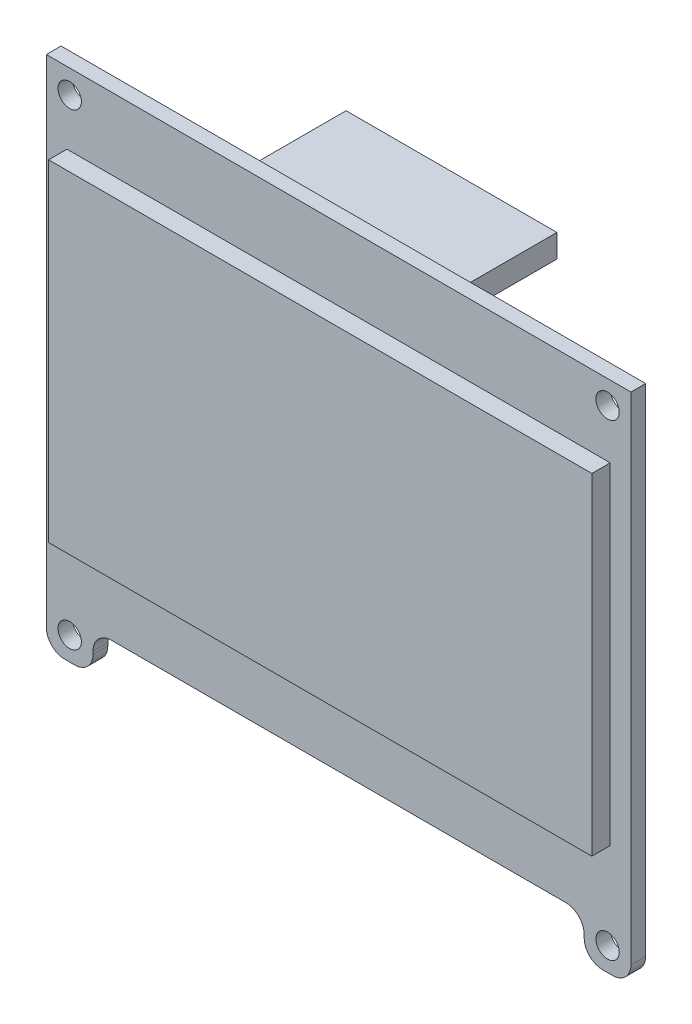
SolidWorks part; units mm, degrees
ref_plane "Front Plane" through (0, 0, 0) normal (0, 0, 1) x (1, 0, 0)
ref_plane "Top Plane" through (0, 0, 0) normal (0, 1, 0) x (1, 0, 0)
ref_plane "Right Plane" through (0, 0, 0) normal (1, 0, 0) x (0, 0, -1)
sketch "Sketch1" plane through (0, 0, 0) normal (0, 0, 1) x (1, 0, 0)
  line L0 (2.54, -53.34) -> (2.54, -55.88) construction
  line L1 (0, 0) -> (63.5, 0)
  line L2 (0, 0) -> (0, -53.88)
  line L3 (2, -55.88) -> (3.08, -55.88)
  line L4 (63.5, 0) -> (63.5, -53.88)
  line L5 (2.54, -53.34) -> (0, -53.34) construction
  line L6 (60.96, -2.54) -> (60.96, 0) construction
  line L7 (60.96, -2.54) -> (63.5, -2.54) construction
  line L8 (2.54, -2.54) -> (60.96, -2.54) construction
  line L9 (0, -25.781) -> (2.25, -25.781) construction
  line L10 (2.25, -7.781) -> (61.25, -7.781)
  line L11 (2.25, -7.781) -> (2.25, -43.781)
  line L12 (2.25, -43.781) -> (61.25, -43.781)
  line L13 (61.25, -7.781) -> (61.25, -43.781)
  line L14 (61.25, -25.781) -> (63.5, -25.781) construction
  line L15 (7.08, -51.562) -> (56.42, -51.562)
  line L16 (31.75, -7.781) -> (31.75, 0) construction
  line L21 (31.75, -43.781) -> (31.75, -51.562) construction
  line L22 (5.08, -53.88) -> (5.08, -53.562)
  line L23 (2.54, -53.34) -> (5.08, -53.34) construction
  line L24 (58.42, -53.88) -> (58.42, -53.562)
  line L25 (60.96, -53.34) -> (58.42, -53.34) construction
  line L26 (60.42, -55.88) -> (61.5, -55.88)
  circle A0 centre (2.54, -2.54) radius 1.27
  circle A1 centre (60.96, -2.54) radius 1.27
  circle A2 centre (60.96, -53.34) radius 1.27
  circle A3 centre (2.54, -53.34) radius 1.27
  arc A4 (61.5, -55.88) -> (63.5, -53.88) centre (61.5, -53.88) ccw
  arc A5 (58.42, -53.88) -> (60.42, -55.88) centre (60.42, -53.88) ccw
  arc A6 (56.42, -51.562) -> (58.42, -53.562) centre (56.42, -53.562) cw
  arc A7 (5.08, -53.562) -> (7.08, -51.562) centre (7.08, -53.562) cw
  arc A8 (5.08, -53.88) -> (3.08, -55.88) centre (3.08, -53.88) cw
  arc A9 (0, -53.88) -> (2, -55.88) centre (2, -53.88) ccw
  point P0 (0, 0)
  point P27 (0, 0)
  point P41 (58.42, -55.88)
  point P50 (0, -55.88)
  dimension "D4" = 2.54
  dimension "D7" = 2
  dimension "D1" = 63.5
  dimension "D2" = 55.88
  dimension "D3" = 50.8
  dimension "D5" = 36
  dimension "D6" = 59
  dimension "D8" = 51.562
extrude "Boss-Extrude1" add sketch "Sketch1" along normal blind 1.6 contours L13 L10 L11 L12 | L2 A9 L3 A8 L22 A7 L15 A6 L24 A5 L26 A4 L4 L1 L10 L13 L12 L11 A0 A1 A2 A3 region at (31.75, -0.8459, 0) region at (31.75, -25.781, 0)
extrude "Boss-Extrude2" add sketch "Sketch1<4>" along normal offset from surface (3.6 mm away) 2 contours L10 L13 L12 L11 up to face at (3.81, -2.54, 1.6) offset beyond the face yes
sketch "Sketch1<4>" plane through (0, 0, 0) normal (0, 0, 1) x (1, 0, 0) same geometry as "Sketch1"
sketch "Sketch2" plane through (0, 0, 0) normal (0, 0, -1) x (-1, 0, 0)
  line L0 (-63.5, -2.5214) -> (0, -2.5214) construction
  line L1 (-63.5, 0) -> (-63.5, -53.88) construction
  line L2 (0, 0) -> (0, -53.88) construction
  line L4 (-43.2, -1.2664) -> (-20.3, -1.2664)
  line L5 (-43.2, -1.2664) -> (-43.2, -3.7764)
  line L6 (-43.2, -3.7764) -> (-20.3, -3.7764)
  line L7 (-20.3, -1.2664) -> (-20.3, -3.7764)
  line L8 (-43.2, -1.2664) -> (-20.3, -3.7764) construction
  line L9 (-43.2, -3.7764) -> (-20.3, -1.2664) construction
  point P7 (-31.75, -2.5214)
  dimension "D1" = 2.51
  dimension "D2" = 22.9
extrude "Boss-Extrude3" add sketch "Sketch2" along normal blind 10.66
